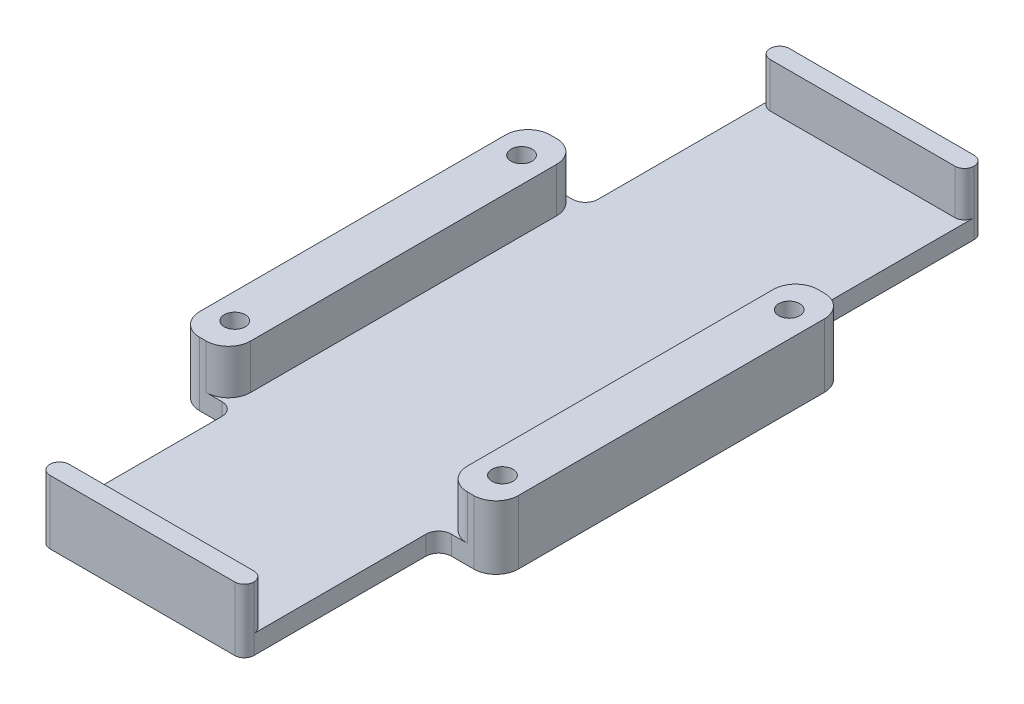
SolidWorks part; units mm, degrees
ref_plane "Спереди" through (0, 0, 0) normal (0, 0, 1) x (1, 0, 0)
ref_plane "Сверху" through (0, 0, 0) normal (0, 1, 0) x (1, 0, 0)
ref_plane "Справа" through (0, 0, 0) normal (1, 0, 0) x (0, 0, -1)
sketch "Эскиз1" plane through (0, 0, 0) normal (0, 1, 0) x (1, 0, 0)
  line L0 (0, 58) -> (0, -58) construction
  line L1 (-25, 58) -> (25, 58)
  line L2 (-25, 58) -> (-25, -58)
  line L3 (-25, -58) -> (25, -58)
  line L4 (25, 58) -> (25, -58)
  line L6 (-25, 0) -> (25, 0) construction
  point P6 (0, 0)
  dimension "D1" = 116
  dimension "D2" = 50
extrude "тело" add sketch "Эскиз1" along normal blind 3
sketch "Эскиз2" plane through (0, 3, 0) normal (0, 1, 0) x (1, 0, 0)
  line L0 (0, 58) -> (0, -58) construction
  line L1 (25, 58) -> (-25, 58) construction
  line L2 (-25, -58) -> (25, -58) construction
  line L4 (-25, 58) -> (-25, -58) construction
  line L5 (-25, 0) -> (25, 0) construction
  line L6 (25, -58) -> (25, 58) construction
  line L7 (-25, 58) -> (-16, 58)
  line L8 (-25, 58) -> (-25, 27.5)
  line L9 (-25, 27.5) -> (-16, 27.5)
  line L10 (-16, 58) -> (-16, 27.5)
  line L11 (25, 58) -> (16, 58)
  line L12 (25, 58) -> (25, 27.5)
  line L13 (25, 27.5) -> (16, 27.5)
  line L14 (16, 58) -> (16, 27.5)
  line L15 (25, -58) -> (16, -58)
  line L16 (25, -58) -> (25, -27.5)
  line L17 (25, -27.5) -> (16, -27.5)
  line L18 (16, -58) -> (16, -27.5)
  line L19 (-25, -58) -> (-16, -58)
  line L20 (-25, -58) -> (-25, -27.5)
  line L21 (-25, -27.5) -> (-16, -27.5)
  line L22 (-16, -58) -> (-16, -27.5)
  dimension "D1" = 55
  dimension "D2" = 32
extrude "пазы чтоб добраться до винтов" cut sketch "Эскиз2" against normal through all
sketch "Эскиз3" plane through (0, 3, 0) normal (0, 1, 0) x (1, 0, 0)
  line L0 (-25, 0) -> (25, 0) construction
  line L1 (-25, 27.5) -> (-25, -27.5) construction
  line L2 (25, -27.5) -> (25, 27.5) construction
  line L3 (0, 58) -> (0, -58) construction
  line L4 (16, 58) -> (-16, 58) construction
  line L5 (-16, -58) -> (16, -58) construction
  line L7 (-25, 27.5) -> (-17, 27.5)
  line L8 (-25, 27.5) -> (-25, -27.5)
  line L9 (-25, -27.5) -> (-17, -27.5)
  line L10 (-17, 27.5) -> (-17, -27.5)
  line L11 (25, 27.5) -> (17, 27.5)
  line L12 (25, 27.5) -> (25, -27.5)
  line L13 (25, -27.5) -> (17, -27.5)
  line L14 (17, 27.5) -> (17, -27.5)
  point P20 (17, 0)
  point P21 (-17, 0)
  dimension "D1" = 34
  dimension "D2" = 55
extrude "крепление к аккумулятору" add sketch "Эскиз3" along normal blind 7
sketch "Эскиз4" plane through (0, 3, 0) normal (0, 1, 0) x (1, 0, 0)
  line L0 (0, 58) -> (0, -58) construction
  line L1 (16, 58) -> (-16, 58) construction
  line L2 (-16, -58) -> (16, -58) construction
  line L3 (16, 58) -> (16, 27.5) construction
  line L4 (-16, 58) -> (16, 58)
  line L5 (-16, 58) -> (-16, 55)
  line L6 (-16, 55) -> (16, 55)
  line L7 (16, 58) -> (16, 55)
  line L8 (-16, -58) -> (16, -58)
  line L9 (-16, -58) -> (-16, -55)
  line L10 (-16, -55) -> (16, -55)
  line L11 (16, -58) -> (16, -55)
  point P14 (0, -55)
  point P15 (0, 55)
  dimension "D2" = 110
extrude "выступы фиксации аккума" add sketch "Эскиз4" along normal blind 7
sketch "Эскиз5" plane through (0, 10, 0) normal (0, 1, 0) x (1, 0, 0)
  line L0 (-25, 0) -> (25, 0) construction
  line L1 (-25, 27.5) -> (-25, -27.5) construction
  line L2 (25, -27.5) -> (25, 27.5) construction
  line L3 (-21, 27.5) -> (-21, -27.5) construction
  line L4 (16, 58) -> (-16, 58) construction
  line L5 (0, 58) -> (0, -58) construction
  line L6 (-16, -58) -> (16, -58) construction
  line L7 (-17, 27.5) -> (-25, 27.5) construction
  line L8 (-25, -27.5) -> (-17, -27.5) construction
  line L10 (25, 27.5) -> (17, 27.5) construction
  line L11 (21, 27.5) -> (21, -27.5) construction
  line L12 (17, -27.5) -> (25, -27.5) construction
  circle A0 centre (-21, 22.5) radius 1.65
  circle A1 centre (-21, -22.5) radius 1.65
  circle A2 centre (21, -22.5) radius 1.65
  circle A3 centre (21, 22.5) radius 1.65
  dimension "D1" = 3.3
  dimension "D2" = 45
extrude "отверстия для шурупов" cut sketch "Эскиз5" against normal through all
sketch "Эскиз7" plane through (0, 0, 0) normal (0, -1, 0) x (1, 0, 0)
  circle A0 centre (-21, 22.5) radius 3.2
  circle A1 centre (-21, -22.5) radius 3.2
  circle A2 centre (21, 22.5) radius 3.2
  circle A3 centre (21, -22.5) radius 3.2
  dimension "D1" = 6.4
extrude "углубления для шляпок" cut sketch "Эскиз7" against normal blind 4
chamfer "Фаска1" [suppressed] distance 1.5 angle 45
fillet "Скругление1" radius 1.5 8 edges at (-16, 6.5, 55) (-16, 5, 58) (16, 5, 58) (16, 6.5, 55) (16, 5, -58) (16, 6.5, -55) (-16, 6.5, -55) (-16, 5, -58)
fillet "Скругление3" radius 3.5 8 edges at (-17, 6.5, 27.5) (-25, 5, 27.5) (-25, 5, -27.5) (-17, 6.5, -27.5) (25, 5, -27.5) (17, 6.5, -27.5) (17, 6.5, 27.5) (25, 5, 27.5)
fillet "Скругление2" radius 2 4 edges at (16, 1.5, -27.5) (-16, 1.5, -27.5) (-16, 1.5, 27.5) (16, 1.5, 27.5)
